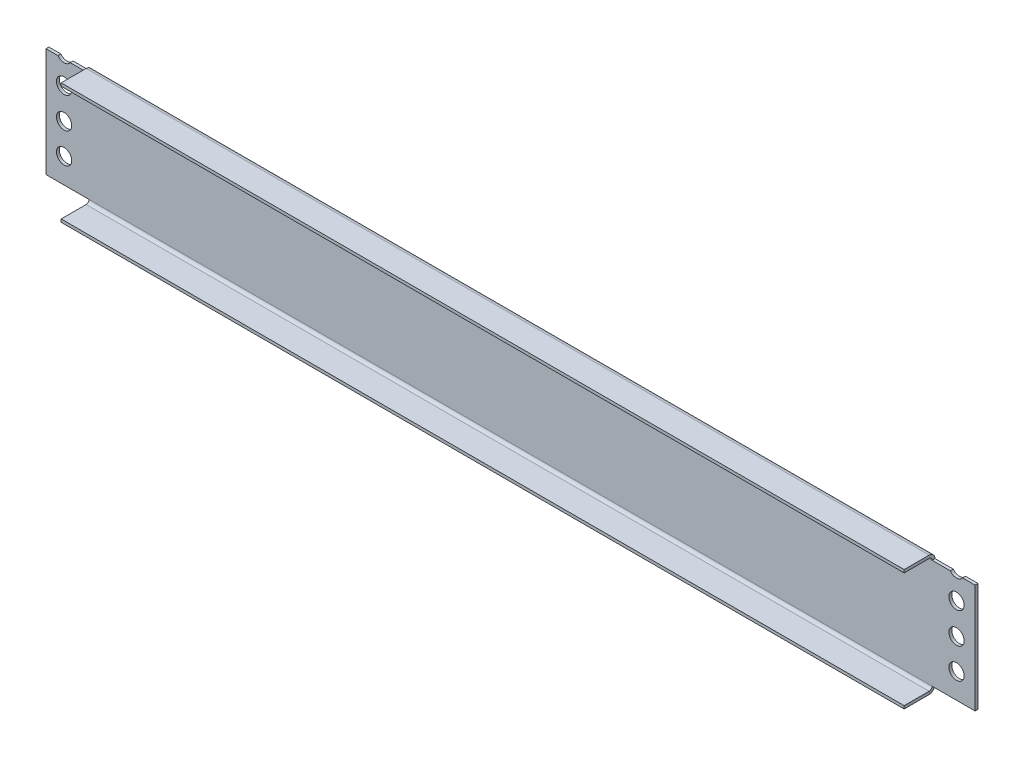
SolidWorks part; units mm, degrees
note: The reader was unsure of these and kept them because the rebuilt part matched: flange length of "Brida de arista1".
ref_plane "Alzado" through (0, 0, 0) normal (0, 0, 1) x (1, 0, 0)
ref_plane "Planta" through (0, 0, 0) normal (0, 1, 0) x (1, 0, 0)
ref_plane "Vista lateral" through (0, 0, 0) normal (1, 0, 0) x (0, 0, -1)
sketch "Croquis1" plane through (0, 0, 0) normal (0, 0, 1) x (1, 0, 0)
  line L1 (-241.3, 31.369) -> (241.3, 31.369)
  line L2 (-241.3, 31.369) -> (-241.3, -31.369)
  line L3 (-241.3, -31.369) -> (241.3, -31.369)
  line L4 (241.3, 31.369) -> (241.3, -31.369)
  line L5 (-241.3, 31.369) -> (241.3, -31.369) construction
  line L6 (-241.3, -31.369) -> (241.3, 31.369) construction
  point P0 (0, 0)
  dimension "D1" = 482.6
  dimension "D2" = 62.738
base flange "Brida base1" sketch "Croquis1" thickness 1.524 reverse thickness direction no parameters "D1"=2.667
edge flange "Brida de arista1" sketch "Croquis10" flange profiles "Croquis10", "Croquis11" flange angle 90 flange length 16.002 flange position material inside bend radius 1.524 thickness 1.524 relief rectangular parameters "D6"=10, "D8"=1
sketch "Croquis10" plane through (0, 31.369, 0) normal (0, 1, 0) x (-1, 0, 0)
  line L2 (-241.3, 0) -> (-241.3, 14.478)
  line L3 (-241.3, 14.478) -> (241.3, 14.478)
  line L4 (241.3, 14.478) -> (241.3, 0)
  line L7 (-241.3, 0) -> (241.3, 0) construction
  line L8 (-241.3, 0) -> (241.3, 0)
sketch "Croquis11" plane through (0, -31.369, 0) normal (0, -1, 0) x (1, 0, 0)
  line L2 (241.3, 0) -> (241.3, 14.478)
  line L3 (241.3, 14.478) -> (-241.3, 14.478)
  line L4 (-241.3, 14.478) -> (-241.3, 0)
  line L5 (-241.3, 0) -> (241.3, 0) construction
  line L6 (-241.3, 0) -> (241.3, 0)
bend "Pliegue de arista1" bend radius 1.524 bend angle 90 parameters "D5"=1
bend "Pliegue de arista2" bend radius 1.524 bend angle 90 parameters "D5"=2
sketch "Croquis12" plane through (0, 0, 0) normal (0, 0, 1) x (1, 0, 0)
  line L0 (241.3, -28.321) -> (241.3, 28.321) construction
  line L1 (241.3, -31.369) -> (-241.3, -31.369) construction
  circle A0 centre (231.648, 16.383) radius 3.9624
  circle A1 centre (231.648, 0.381) radius 3.9624
  circle A2 centre (231.648, -15.367) radius 3.9624
  circle A3 centre (-231.902, 16.383) radius 3.9624
  circle A4 centre (-231.902, 0.381) radius 3.9624
  circle A5 centre (-231.902, -15.367) radius 3.9624
  dimension "D7" = 7.9248
  dimension "D8" = 7.9248
  dimension "D9" = 7.9248
  dimension "D16" = 7.9248
  dimension "D17" = 7.9248
  dimension "D18" = 7.9248
  dimension "D1" = 9.652
  dimension "D2" = 9.652
  dimension "D3" = 9.652
  dimension "D4" = 16.002
  dimension "D5" = 31.75
  dimension "D6" = 47.752
  dimension "D10" = 473.202
  dimension "D11" = 473.202
  dimension "D12" = 473.202
  dimension "D13" = 16.002
  dimension "D14" = 31.75
  dimension "D15" = 47.752
extrude "Cortar-Extruir1" cut sketch "Croquis12" against normal blind 58.166 normal cut yes
sketch "Croquis13" plane through (0, 31.369, 0) normal (0, 1, 0) x (1, 0, 0)
  line L0 (241.3, -14.478) -> (241.3, -1.524) construction
  line L1 (218.948, 1.524) -> (241.3, 1.524)
  line L2 (218.948, 1.524) -> (218.948, -14.478)
  line L3 (218.948, -14.478) -> (241.3, -14.478)
  line L4 (241.3, 1.524) -> (241.3, -14.478)
  line L5 (218.948, 1.524) -> (241.3, -14.478) construction
  line L6 (218.948, -14.478) -> (241.3, 1.524) construction
  line L7 (-241.3, 1.524) -> (241.3, 1.524) construction
  line L8 (-241.3, -14.478) -> (241.3, -14.478) construction
  line L9 (-241.3, -1.524) -> (-241.3, -14.478) construction
  line L10 (-241.3, 1.524) -> (-218.948, 1.524)
  line L11 (-241.3, 1.524) -> (-241.3, -14.478)
  line L12 (-241.3, -14.478) -> (-218.948, -14.478)
  line L13 (-218.948, 1.524) -> (-218.948, -14.478)
  line L14 (-241.3, 1.524) -> (-218.948, -14.478) construction
  line L15 (-241.3, -14.478) -> (-218.948, 1.524) construction
  point P0 (230.124, -6.477)
  point P11 (-230.124, -6.477)
  dimension "D1" = 22.352
  dimension "D2" = 22.352
extrude "Cortar-Extruir2" cut sketch "Croquis13" along normal blind 1.016 and the other way blind 3.048 normal cut yes
sketch "Croquis14" plane through (0, -31.369, 0) normal (0, -1, 0) x (1, 0, 0)
  line L0 (-241.3, 14.478) -> (-241.3, 1.524) construction
  line L1 (-241.3, 14.478) -> (-218.948, 14.478)
  line L2 (-241.3, 14.478) -> (-241.3, -1.524)
  line L3 (-241.3, -1.524) -> (-218.948, -1.524)
  line L4 (-218.948, 14.478) -> (-218.948, -1.524)
  line L5 (-241.3, 14.478) -> (-218.948, -1.524) construction
  line L6 (-241.3, -1.524) -> (-218.948, 14.478) construction
  line L7 (241.3, 14.478) -> (-241.3, 14.478) construction
  line L8 (241.3, -1.524) -> (-241.3, -1.524) construction
  line L9 (241.3, 1.524) -> (241.3, 14.478) construction
  line L10 (218.948, 14.478) -> (241.3, 14.478)
  line L11 (218.948, 14.478) -> (218.948, -1.524)
  line L12 (218.948, -1.524) -> (241.3, -1.524)
  line L13 (241.3, 14.478) -> (241.3, -1.524)
  line L14 (218.948, 14.478) -> (241.3, -1.524) construction
  line L15 (218.948, -1.524) -> (241.3, 14.478) construction
  point P0 (-230.124, 6.477)
  point P11 (230.124, 6.477)
  dimension "D1" = 22.352
  dimension "D2" = 22.352
extrude "Cortar-Extruir3" cut sketch "Croquis14" against normal blind 3.048 normal cut yes
sketch "Croquis15" plane through (0, 0, 0) normal (0, 0, 1) x (1, 0, 0)
  line L4 (218.948, 29.845) -> (-218.948, 29.845) construction
  line L5 (-218.948, 29.845) -> (218.948, 29.845) construction
  line L6 (241.3, -28.321) -> (241.3, 28.321) construction
  circle A2 centre (-231.902, 30.6324) radius 3.937
  circle A3 centre (231.648, 30.6324) radius 3.937
  dimension "D1" = 7.874
  dimension "D2" = 0.7874
  dimension "D4" = 7.874
  dimension "D3" = 0.7874
  dimension "D5" = 9.652
  dimension "D6" = 473.202
extrude "Cortar-Extruir4" cut sketch "Croquis15" against normal blind 2.794 normal cut yes
sketch "Líneas de pliegue1" [suppressed] plane through (0, 0, 0) normal (0, 1, 0) x (1, 0, 0)
sketch "Cuadro delimitador1" [suppressed] plane through (0, 0, 0) normal (0, 1, 0) x (1, 0, 0)
sheet metal parameters "Chapa metálica1" thickness 1.524 parameters "D1"=2.667
flat pattern "Chapa desplegada1" [suppressed]
sketch "Líneas de pliegue2" plane through (0, 0, 0) normal (0, 1, 0) x (1, 0, 0)
sketch3d "Cuadro delimitador2" [suppressed]
  line L0 (241.3, -31.369, 0) -> (-241.3, -31.369, 0) construction
  line L1 (241.3, 31.369, 0) -> (-241.3, 31.369, 0) construction
  line L2 (241.3, -31.369, 0) -> (241.3, 31.369, 0) construction
  line L3 (-241.3, -31.369, 0) -> (-241.3, 31.369, 0) construction
sheet metal parameters "Chapa metálica2" thickness 1.524 parameters "D1"=2.667
flat pattern "Chapa desplegada1"
sketch "Líneas de pliegue2" plane through (0, 0, 0) normal (0, 0, 1) x (1, 0, 0)
  line L0 (-241.3, -30.0805) -> (241.3, -30.0805) construction
  line L1 (241.3, 30.0805) -> (-241.3, 30.0805) construction
  line L2 (-241.3, -30.0805) -> (241.3, -30.0805) construction
  line L3 (241.3, 30.0805) -> (-241.3, 30.0805) construction
sketch3d "Cuadro delimitador2" [suppressed]
  line L0 (-241.3, -44.794, 0) -> (241.3, -44.794, 0) construction
  line L1 (-241.3, 44.794, 0) -> (241.3, 44.794, 0) construction
  line L2 (-241.3, -44.794, 0) -> (-241.3, 44.794, 0) construction
  line L3 (241.3, -44.794, 0) -> (241.3, 44.794, 0) construction
bend of the flat pattern "Aplanar-<Pliegue de arista1>1"
bend of the flat pattern "Aplanar-<Pliegue de arista2>1"
sheet metal parameters "Chapa metálica3" thickness 1.524 parameters "D1"=2.667
flat pattern "Chapa desplegada1"
sketch "Líneas de pliegue2" plane through (0, 0, 0) normal (0, 0, 1) x (1, 0, 0)
  line L0 (-241.3, -30.0805) -> (241.3, -30.0805) construction
  line L1 (241.3, 30.0805) -> (-241.3, 30.0805) construction
  line L2 (-241.3, -30.0805) -> (241.3, -30.0805) construction
  line L3 (241.3, 30.0805) -> (-241.3, 30.0805) construction
sketch3d "Cuadro delimitador2" [suppressed]
  line L0 (-241.3, -44.794, 0) -> (241.3, -44.794, 0) construction
  line L1 (-241.3, 44.794, 0) -> (241.3, 44.794, 0) construction
  line L2 (-241.3, -44.794, 0) -> (-241.3, 44.794, 0) construction
  line L3 (241.3, -44.794, 0) -> (241.3, 44.794, 0) construction
bend of the flat pattern "Aplanar-<Pliegue de arista1>1"
bend of the flat pattern "Aplanar-<Pliegue de arista2>1"
sheet metal parameters "Chapa metálica4" thickness 1.524 parameters "D1"=2.667
flat pattern "Chapa desplegada1"
sketch "Líneas de pliegue2" plane through (0, 0, 0) normal (0, 0, 1) x (1, 0, 0)
  line L0 (-241.3, -30.0805) -> (241.3, -30.0805) construction
  line L1 (218.948, 30.0805) -> (-218.948, 30.0805) construction
  line L2 (-241.3, -30.0805) -> (241.3, -30.0805) construction
  line L3 (218.948, 30.0805) -> (-218.948, 30.0805) construction
sketch3d "Cuadro delimitador2" [suppressed]
  line L0 (-241.3, -44.794, 0) -> (241.3, -44.794, 0) construction
  line L1 (-241.3, 44.794, 0) -> (241.3, 44.794, 0) construction
  line L2 (-241.3, -44.794, 0) -> (-241.3, 44.794, 0) construction
  line L3 (241.3, -44.794, 0) -> (241.3, 44.794, 0) construction
bend of the flat pattern "Aplanar-<Pliegue de arista1>1"
bend of the flat pattern "Aplanar-<Pliegue de arista2>1"
sheet metal parameters "Chapa metálica5" thickness 1.524 parameters "D1"=2.667
flat pattern "Chapa desplegada1"
sketch "Líneas de pliegue2" plane through (0, 0, 0) normal (0, 0, 1) x (1, 0, 0)
  line L0 (-218.948, -30.0805) -> (218.948, -30.0805) construction
  line L1 (218.948, 30.0805) -> (-218.948, 30.0805) construction
  line L2 (-218.948, -30.0805) -> (218.948, -30.0805) construction
  line L3 (218.948, 30.0805) -> (-218.948, 30.0805) construction
sketch3d "Cuadro delimitador2" [suppressed]
  line L0 (-241.3, -44.794, 0) -> (241.3, -44.794, 0) construction
  line L1 (-241.3, 44.794, 0) -> (241.3, 44.794, 0) construction
  line L2 (-241.3, -44.794, 0) -> (-241.3, 44.794, 0) construction
  line L3 (241.3, -44.794, 0) -> (241.3, 44.794, 0) construction
bend of the flat pattern "Aplanar-<Pliegue de arista1>1"
bend of the flat pattern "Aplanar-<Pliegue de arista2>1"
sheet metal parameters "Chapa metálica6" thickness 1.524 parameters "D1"=2.667
flat pattern "Chapa desplegada1"
sketch "Líneas de pliegue2" plane through (0, 0, 0) normal (0, 0, 1) x (1, 0, 0)
  line L0 (-218.948, -30.0805) -> (218.948, -30.0805) construction
  line L1 (218.948, 30.0805) -> (-218.948, 30.0805) construction
  line L2 (-218.948, -30.0805) -> (218.948, -30.0805) construction
  line L3 (218.948, 30.0805) -> (-218.948, 30.0805) construction
sketch3d "Cuadro delimitador2" [suppressed]
  line L0 (-241.3, -44.794, 0) -> (241.3, -44.794, 0) construction
  line L1 (-241.3, 44.794, 0) -> (241.3, 44.794, 0) construction
  line L2 (-241.3, -44.794, 0) -> (-241.3, 44.794, 0) construction
  line L3 (241.3, -44.794, 0) -> (241.3, 44.794, 0) construction
bend of the flat pattern "Aplanar-<Pliegue de arista1>1"
bend of the flat pattern "Aplanar-<Pliegue de arista2>1"
